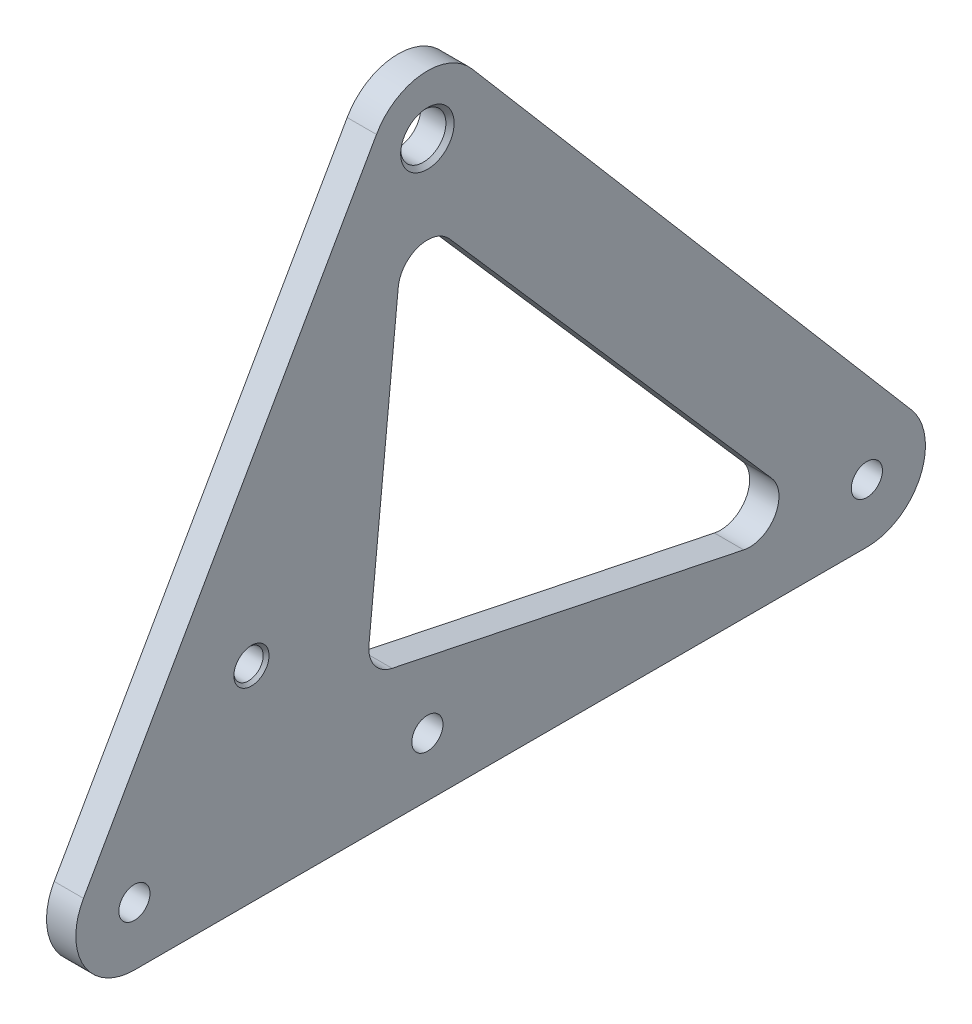
SolidWorks part; units mm, degrees
material "1060 Alloy"
ref_plane "Front Plane" through (0, 0, 0) normal (0, 0, 1) x (1, 0, 0)
ref_plane "Top Plane" through (0, 0, 0) normal (0, 1, 0) x (1, 0, 0)
ref_plane "Right Plane" through (0, 0, 0) normal (1, 0, 0) x (0, 0, -1)
sketch "Sketch1" plane through (0, 0, 0) normal (1, 0, 0) x (0, 0, -1)
  line L0 (-74.539, -105.3537) -> (-11.039, 6.2793)
  line L1 (9.6612, 8.2433) -> (104.9112, -103.3897)
  line L2 (-63.5, -124.333) -> (95.25, -124.333)
  arc A0 (9.6612, 8.2433) -> (-11.039, 6.2793) centre (0, 0) ccw
  arc A1 (95.25, -124.333) -> (104.9112, -103.3897) centre (95.25, -111.633) ccw
  arc A2 (-74.539, -105.3537) -> (-63.5, -124.333) centre (-63.5, -111.633) ccw
  dimension "D1" = 158.75
  dimension "D2" = 111.633
  dimension "D4" = 25.4
  dimension "D5" = 95.25
extrude "Boss-Extrude1" add sketch "Sketch1" along normal blind 6.35 contours L1 A1 L2 A2 L0 A0
sketch "Sketch2" plane through (6.35, 0, 0) normal (1, 0, 0) x (0, 0, -1)
  circle A0 centre (-63.5, -111.633) radius 3.3782
  circle A1 centre (0, -111.633) radius 3.3782
  circle A2 centre (95.25, -111.633) radius 3.3782
  arc A3 (-74.539, -105.3537) -> (-63.5, -124.333) centre (-63.5, -111.633) ccw construction
  arc A4 (95.25, -124.333) -> (104.9112, -103.3897) centre (95.25, -111.633) ccw construction
  dimension "D2" = 0
  dimension "D3" = 0
  dimension "D4" = 63.5
  dimension "D5" = 6.7564
extrude "Cut-Extrude1" cut sketch "Sketch2" against normal up to next
hole_wizard "3/8 Clearance Hole1" positions "Sketch3" profile "Sketch4" hole size "3/8" standard "ANSI Inch" end condition through all
sketch "Sketch3" plane through (6.35, 0, 0) normal (1, 0, 0) x (0, 0, -1)
  point P0 (0, 0)
sketch "Sketch4" plane through (6.35, 0, 0) normal (0, 1, 0) x (0, 0, -1)
  line L0 (0, 0) -> (0, 6.35)
  line L1 (0, 6.35) -> (4.9022, 6.35)
  line L2 (4.9022, 6.35) -> (4.9022, 0.8915)
  line L3 (4.9022, 0.8915) -> (5.7937, 0)
  line L5 (5.7937, 0) -> (0, 0)
  line L6 (-4.9022, 0.8915) -> (-5.7937, 0) construction
  line L11 (0, -6.35) -> (0, 107.95) construction
  dimension "Thru Hole Dia." = 9.8044
  dimension "Thru Hole Depth" = 6.35
  dimension "Near C'Sink Dia." = 11.5875
  dimension "Near C'Sink Angle" = 90
hole_wizard "1/4 (0.2500) Dowel Hole1" positions "Sketch5" profile "Sketch6" hole size "1/4" standard "ANSI Inch" end condition through all
sketch "Sketch5" plane through (6.35, 0, 0) normal (1, 0, 0) x (0, 0, -1)
  line L0 (-63.5, -124.333) -> (95.25, -124.333) construction
  line L1 (-74.539, -105.3537) -> (-11.039, 6.2793) construction
  point P0 (-38.1343, -79.883)
  dimension "D1" = 44.45
  dimension "D2" = 19.05
sketch "Sketch6" plane through (6.35, -79.883, 38.1343) normal (0, 1, 0) x (0, 0, -1)
  line L0 (0, 0) -> (0, 6.35)
  line L1 (0, 6.35) -> (3.175, 6.35)
  line L2 (3.175, 6.35) -> (3.175, 0.635)
  line L3 (3.175, 0.635) -> (3.81, 0)
  line L5 (3.81, 0) -> (0, 0)
  line L6 (-3.175, 0.635) -> (-3.81, 0) construction
  line L11 (0, -6.35) -> (0, 107.95) construction
  dimension "Thru Hole Dia." = 6.35
  dimension "Thru Hole Depth" = 6.35
  dimension "Near C'Sink Dia." = 7.62
  dimension "Near C'Sink Angle" = 90
sketch "Sketch7" plane through (6.35, 0, 0) normal (1, 0, 0) x (0, 0, -1)
  line L0 (-6.319, -24.7731) -> (-12.669, -88.7811)
  line L1 (-7.6451, -95.6245) -> (68.5549, -111.4995)
  line L2 (74.6303, -101.1031) -> (4.7803, -21.2201)
  arc A0 (4.7803, -21.2201) -> (-6.319, -24.7731) centre (0, -25.4) ccw
  arc A1 (68.5549, -111.4995) -> (74.6303, -101.1031) centre (69.85, -105.283) ccw
  arc A2 (-12.669, -88.7811) -> (-7.6451, -95.6245) centre (-6.35, -89.408) ccw
  circle A3 centre (0, 0) radius 4.9022 construction
  circle A5 centre (95.25, -111.633) radius 3.3782 construction
  circle A7 centre (0, -111.633) radius 3.3782 construction
  point P5 (79.2331, -126.3342)
  point P7 (83.7446, -122.0188)
  point P10 (0, 0)
  point P12 (-13.2116, 2.46)
  point P14 (0, 0)
  point P19 (0, 0)
  point P20 (0, 0)
  point P23 (0, 0)
  point P24 (0, 0)
  dimension "D1" = 25.4
  dimension "D2" = 25.4
  dimension "D3" = 6.35
  dimension "D4" = 22.225
  dimension "D5" = 6.35
  dimension "D6" = 6.35
extrude "Cut-Extrude2" cut sketch "Sketch7" against normal through all
